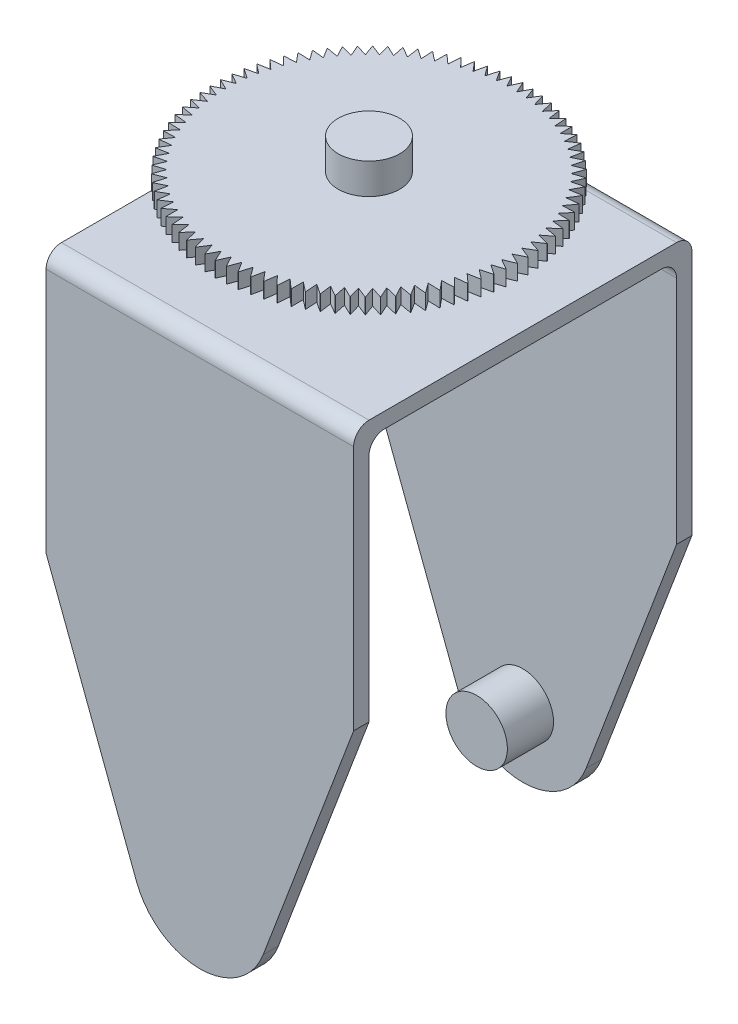
SolidWorks part; units mm, degrees
material "AISI 1035 Steel (SS)"
ref_plane "Front Plane" through (0, 0, 0) normal (0, 0, 1) x (1, 0, 0)
ref_plane "Top Plane" through (0, 0, 0) normal (0, 1, 0) x (1, 0, 0)
ref_plane "Right Plane" through (0, 0, 0) normal (1, 0, 0) x (0, 0, -1)
sketch "Sketch3" plane through (0, 0, 0) normal (0, 0, 1) x (1, 0, 0)
  line L0 (-50, 150) -> (50, 150)
  line L1 (50, 150) -> (50, 70)
  line L2 (50, 70) -> (20.5771, -7.7836)
  line L3 (-50, 150) -> (-50, 70)
  line L4 (-50, 70) -> (-20.5771, -7.7836)
  arc A0 (-20.5771, -7.7836) -> (20.5771, -7.7836) centre (0, 0) ccw
  point P7 (0, 150)
  dimension "D1" = 150
  dimension "D3" = 22
  dimension "D2" = 100
  dimension "D4" = 80
extrude "Boss-Extrude1" add sketch "Sketch3" along normal blind 5
sketch "Sketch4" plane through (0, 0, 5) normal (0, 0, 1) x (1, 0, 0)
  circle A0 centre (0, 0) radius 10
  dimension "D1" = 20
extrude "Boss-Extrude2" add sketch "Sketch4" along normal blind 15
sketch "Sketch5" plane through (0, 0, 0) normal (0, 0, -1) x (-1, 0, 0)
  line L0 (50, 150) -> (50, 70) construction
  line L1 (-50, 150) -> (50, 150)
  line L2 (-50, 150) -> (-50, 155)
  line L3 (-50, 155) -> (50, 155)
  line L4 (50, 150) -> (50, 155)
  dimension "D1" = 5
extrude "Boss-Extrude3" add sketch "Sketch5" against normal blind 55
mirror "Mirror1" about plane through (0, 0, 55) normal (0, 0, 1) of bodies 103
fillet "Fillet1" radius 5 4 edges at (0, 150, 105) (0, 150, 5) (0, 155, 110) (0, 155, 0)
sketch "Sketch6" plane through (0, 155, 0) normal (0, 1, 0) x (1, 0, 0)
  line L0 (50, -5) -> (-50, -5) construction
  line L1 (-50, -105) -> (-50, -5) construction
  circle A0 centre (0, -55) radius 12.5
  point P5 (0, -5)
  point P9 (-50, -55)
  dimension "D1" = 25
extrude "Boss-Extrude4" add sketch "Sketch6" along normal blind 5
sketch "Sketch7" plane through (0, 160, 0) normal (0, 1, 0) x (1, 0, 0)
  circle A0 centre (0, -55) radius 10
  circle A1 centre (0, -55) radius 12.5 construction
  dimension "D1" = 20
extrude "Boss-Extrude5" add sketch "Sketch7" along normal blind 5
sketch "Sketch8" plane through (0, 165, 0) normal (0, 1, 0) x (1, 0, 0)
  circle A0 centre (0, -55) radius 12.5 construction
  circle A1 centre (0, -55) radius 12.5
extrude "Boss-Extrude6" add sketch "Sketch8" along normal blind 5
sketch "Sketch9" plane through (0, 170, 0) normal (0, 1, 0) x (1, 0, 0)
  line L0 (0, -5) -> (1.5929, -8.5336)
  line L1 (1.5929, -8.5336) -> (3.4241, -5.1174)
  line L2 (4.8304, -8.7579) -> (6.8954, -5.4777)
  line L3 (3.4878, -5.1218) -> (4.8304, -8.7579)
  line L4 (8.0443, -9.2075) -> (10.3331, -6.0794)
  line L5 (6.9587, -5.4866) -> (8.0443, -9.2075)
  line L6 (11.219, -9.8802) -> (13.7204, -6.9193)
  line L7 (10.3956, -6.0926) -> (11.219, -9.8802)
  line L8 (14.3391, -10.7727) -> (17.0409, -7.9936)
  line L9 (13.7819, -6.9369) -> (14.3391, -10.7727)
  line L10 (17.3893, -11.8807) -> (20.2784, -9.2968)
  line L11 (17.101, -8.0154) -> (17.3893, -11.8807)
  line L12 (20.3548, -13.1987) -> (23.4171, -10.8227)
  line L13 (20.3368, -9.3227) -> (20.3548, -13.1987)
  line L14 (23.2211, -14.7204) -> (26.4417, -12.5638)
  line L15 (23.4736, -10.8526) -> (23.2211, -14.7204)
  line L16 (25.9743, -16.4384) -> (29.3375, -14.5116)
  line L17 (26.496, -12.5976) -> (25.9743, -16.4384)
  line L18 (28.601, -18.3442) -> (32.0904, -16.6567)
  line L19 (29.3893, -14.5492) -> (28.601, -18.3442)
  line L20 (31.0883, -20.4286) -> (34.6869, -18.9886)
  line L21 (32.1394, -16.6978) -> (31.0883, -20.4286)
  line L22 (33.4241, -22.6814) -> (37.1145, -21.496)
  line L23 (34.7329, -19.033) -> (33.4241, -22.6814)
  line L24 (35.5971, -25.0917) -> (39.3612, -24.1666)
  line L25 (37.1572, -21.5435) -> (35.5971, -25.0917)
  line L26 (37.5967, -27.6477) -> (41.4161, -26.9874)
  line L27 (39.4005, -24.2169) -> (37.5967, -27.6477)
  line L28 (39.4131, -30.3369) -> (43.2693, -29.9447)
  line L29 (41.4519, -27.0404) -> (39.4131, -30.3369)
  line L30 (41.0375, -33.1463) -> (44.9117, -33.024)
  line L31 (43.3013, -30) -> (41.0375, -33.1463)
  line L32 (42.462, -36.0622) -> (46.3352, -36.2104)
  line L33 (44.9397, -33.0814) -> (42.462, -36.0622)
  line L34 (43.6796, -39.0703) -> (47.533, -39.4884)
  line L35 (46.3592, -36.2697) -> (43.6796, -39.0703)
  line L36 (44.6844, -42.156) -> (48.4993, -42.8419)
  line L37 (47.5528, -39.5492) -> (44.6844, -42.156)
  line L38 (45.4715, -45.3044) -> (49.2293, -46.2547)
  line L39 (48.5148, -42.9039) -> (45.4715, -45.3044)
  line L40 (46.0371, -48.4999) -> (49.7194, -49.71)
  line L41 (49.2404, -46.3176) -> (46.0371, -48.4999)
  line L42 (46.3784, -51.7271) -> (49.9673, -53.1912)
  line L43 (49.7261, -49.7736) -> (46.3784, -51.7271)
  line L44 (46.4937, -54.9703) -> (49.9717, -56.6811)
  line L45 (49.9695, -53.255) -> (46.4937, -54.9703)
  line L46 (46.3825, -58.2136) -> (49.7327, -60.1629)
  line L47 (49.9695, -56.745) -> (46.3825, -58.2136)
  line L48 (46.0454, -61.4412) -> (49.2514, -63.6195)
  line L49 (49.7261, -60.2264) -> (46.0454, -61.4412)
  line L50 (45.4839, -64.6375) -> (48.5302, -67.0341)
  line L51 (49.2404, -63.6824) -> (45.4839, -64.6375)
  line L52 (44.7008, -67.7868) -> (47.5725, -70.3901)
  line L53 (48.5148, -67.0961) -> (44.7008, -67.7868)
  line L54 (43.6999, -70.8739) -> (46.3831, -73.6711)
  line L55 (47.5528, -70.4508) -> (43.6999, -70.8739)
  line L56 (42.4862, -73.8835) -> (44.9677, -76.8611)
  line L57 (46.3592, -73.7303) -> (42.4862, -73.8835)
  line L58 (41.0654, -76.8012) -> (43.3332, -79.9446)
  line L59 (44.9397, -76.9186) -> (41.0654, -76.8012)
  line L60 (39.4446, -79.6127) -> (41.4876, -82.9066)
  line L61 (43.3013, -80) -> (39.4446, -79.6127)
  line L62 (37.6317, -82.3043) -> (39.4398, -85.7327)
  line L63 (41.4519, -82.9596) -> (37.6317, -82.3043)
  line L64 (35.6353, -84.8628) -> (37.2, -88.409)
  line L65 (39.4005, -85.7831) -> (35.6353, -84.8628)
  line L66 (33.4654, -87.2759) -> (34.7789, -90.9226)
  line L67 (37.1572, -88.4565) -> (33.4654, -87.2759)
  line L68 (31.1324, -89.5317) -> (32.1883, -93.2611)
  line L69 (34.7329, -90.967) -> (31.1324, -89.5317)
  line L70 (28.6478, -91.6192) -> (29.4409, -95.4133)
  line L71 (32.1394, -93.3022) -> (28.6478, -91.6192)
  line L72 (26.0236, -93.5284) -> (26.5501, -97.3685)
  line L73 (29.3893, -95.4508) -> (26.0236, -93.5284)
  line L74 (23.2726, -95.2499) -> (23.53, -99.1173)
  line L75 (26.496, -97.4024) -> (23.2726, -95.2499)
  line L76 (20.4082, -96.7752) -> (20.3952, -100.6512)
  line L77 (23.4736, -99.1474) -> (20.4082, -96.7752)
  line L78 (17.4444, -98.0971) -> (17.161, -101.9627)
  line L79 (20.3368, -100.6773) -> (17.4444, -98.0971)
  line L80 (14.3956, -99.209) -> (13.8433, -103.0454)
  line L81 (17.101, -101.9846) -> (14.3956, -99.209)
  line L82 (11.2767, -100.1054) -> (10.4581, -103.8941)
  line L83 (13.7819, -103.0631) -> (11.2767, -100.1054)
  line L84 (8.1028, -100.7822) -> (7.0219, -104.5045)
  line L85 (10.3956, -103.9074) -> (8.1028, -100.7822)
  line L86 (4.8895, -101.2359) -> (3.5516, -104.8737)
  line L87 (6.9587, -104.5134) -> (4.8895, -101.2359)
  line L88 (1.6523, -101.4643) -> (0.0639, -105)
  line L89 (3.4878, -104.8782) -> (1.6523, -101.4643)
  line L90 (-1.5929, -101.4664) -> (-3.4241, -104.8826)
  line L91 (0, -105) -> (-1.5929, -101.4664)
  line L92 (-4.8304, -101.2421) -> (-6.8954, -104.5223)
  line L93 (-3.4878, -104.8782) -> (-4.8304, -101.2421)
  line L94 (-8.0443, -100.7925) -> (-10.3331, -103.9206)
  line L95 (-6.9587, -104.5134) -> (-8.0443, -100.7925)
  line L96 (-11.219, -100.1198) -> (-13.7204, -103.0807)
  line L97 (-10.3956, -103.9074) -> (-11.219, -100.1198)
  line L98 (-14.3391, -99.2273) -> (-17.0409, -102.0064)
  line L99 (-13.7819, -103.0631) -> (-14.3391, -99.2273)
  line L100 (-17.3893, -98.1193) -> (-20.2784, -100.7032)
  line L101 (-17.101, -101.9846) -> (-17.3893, -98.1193)
  line L102 (-20.3548, -96.8013) -> (-23.4171, -99.1773)
  line L103 (-20.3368, -100.6773) -> (-20.3548, -96.8013)
  line L104 (-23.2211, -95.2796) -> (-26.4417, -97.4362)
  line L105 (-23.4736, -99.1474) -> (-23.2211, -95.2796)
  line L106 (-25.9743, -93.5616) -> (-29.3375, -95.4884)
  line L107 (-26.496, -97.4024) -> (-25.9743, -93.5616)
  line L108 (-28.601, -91.6558) -> (-32.0904, -93.3433)
  line L109 (-29.3893, -95.4508) -> (-28.601, -91.6558)
  line L110 (-31.0883, -89.5714) -> (-34.6869, -91.0114)
  line L111 (-32.1394, -93.3022) -> (-31.0883, -89.5714)
  line L112 (-33.4241, -87.3186) -> (-37.1145, -88.504)
  line L113 (-34.7329, -90.967) -> (-33.4241, -87.3186)
  line L114 (-35.5971, -84.9083) -> (-39.3612, -85.8334)
  line L115 (-37.1572, -88.4565) -> (-35.5971, -84.9083)
  line L116 (-37.5967, -82.3523) -> (-41.4161, -83.0126)
  line L117 (-39.4005, -85.7831) -> (-37.5967, -82.3523)
  line L118 (-39.4131, -79.6631) -> (-43.2693, -80.0553)
  line L119 (-41.4519, -82.9596) -> (-39.4131, -79.6631)
  line L120 (-41.0375, -76.8537) -> (-44.9117, -76.976)
  line L121 (-43.3013, -80) -> (-41.0375, -76.8537)
  line L122 (-42.462, -73.9378) -> (-46.3352, -73.7896)
  line L123 (-44.9397, -76.9186) -> (-42.462, -73.9378)
  line L124 (-43.6796, -70.9297) -> (-47.533, -70.5116)
  line L125 (-46.3592, -73.7303) -> (-43.6796, -70.9297)
  line L126 (-44.6844, -67.844) -> (-48.4993, -67.1581)
  line L127 (-47.5528, -70.4508) -> (-44.6844, -67.844)
  line L128 (-45.4715, -64.6956) -> (-49.2293, -63.7453)
  line L129 (-48.5148, -67.0961) -> (-45.4715, -64.6956)
  line L130 (-46.0371, -61.5001) -> (-49.7194, -60.29)
  line L131 (-49.2404, -63.6824) -> (-46.0371, -61.5001)
  line L132 (-46.3784, -58.2729) -> (-49.9673, -56.8088)
  line L133 (-49.7261, -60.2264) -> (-46.3784, -58.2729)
  line L134 (-46.4937, -55.0297) -> (-49.9717, -53.3189)
  line L135 (-49.9695, -56.745) -> (-46.4937, -55.0297)
  line L136 (-46.3825, -51.7864) -> (-49.7327, -49.8371)
  line L137 (-49.9695, -53.255) -> (-46.3825, -51.7864)
  line L138 (-46.0454, -48.5588) -> (-49.2514, -46.3805)
  line L139 (-49.7261, -49.7736) -> (-46.0454, -48.5588)
  line L140 (-45.4839, -45.3625) -> (-48.5302, -42.9659)
  line L141 (-49.2404, -46.3176) -> (-45.4839, -45.3625)
  line L142 (-44.7008, -42.2132) -> (-47.5725, -39.6099)
  line L143 (-48.5148, -42.9039) -> (-44.7008, -42.2132)
  line L144 (-43.6999, -39.1261) -> (-46.3831, -36.3289)
  line L145 (-47.5528, -39.5492) -> (-43.6999, -39.1261)
  line L146 (-42.4862, -36.1165) -> (-44.9677, -33.1389)
  line L147 (-46.3592, -36.2697) -> (-42.4862, -36.1165)
  line L148 (-41.0654, -33.1988) -> (-43.3332, -30.0554)
  line L149 (-44.9397, -33.0814) -> (-41.0654, -33.1988)
  line L150 (-39.4446, -30.3873) -> (-41.4876, -27.0934)
  line L151 (-43.3013, -30) -> (-39.4446, -30.3873)
  line L152 (-37.6317, -27.6957) -> (-39.4398, -24.2673)
  line L153 (-41.4519, -27.0404) -> (-37.6317, -27.6957)
  line L154 (-35.6353, -25.1372) -> (-37.2, -21.591)
  line L155 (-39.4005, -24.2169) -> (-35.6353, -25.1372)
  line L156 (-33.4654, -22.7241) -> (-34.7789, -19.0774)
  line L157 (-37.1572, -21.5435) -> (-33.4654, -22.7241)
  line L158 (-31.1324, -20.4683) -> (-32.1883, -16.7389)
  line L159 (-34.7329, -19.033) -> (-31.1324, -20.4683)
  line L160 (-28.6478, -18.3808) -> (-29.4409, -14.5867)
  line L161 (-32.1394, -16.6978) -> (-28.6478, -18.3808)
  line L162 (-26.0236, -16.4716) -> (-26.5501, -12.6315)
  line L163 (-29.3893, -14.5492) -> (-26.0236, -16.4716)
  line L164 (-23.2726, -14.7501) -> (-23.53, -10.8827)
  line L165 (-26.496, -12.5976) -> (-23.2726, -14.7501)
  line L166 (-20.4082, -13.2248) -> (-20.3952, -9.3488)
  line L167 (-23.4736, -10.8526) -> (-20.4082, -13.2248)
  line L168 (-17.4444, -11.9029) -> (-17.161, -8.0373)
  line L169 (-20.3368, -9.3227) -> (-17.4444, -11.9029)
  line L170 (-14.3956, -10.791) -> (-13.8433, -6.9546)
  line L171 (-17.101, -8.0154) -> (-14.3956, -10.791)
  line L172 (-11.2767, -9.8946) -> (-10.4581, -6.1059)
  line L173 (-13.7819, -6.9369) -> (-11.2767, -9.8946)
  line L174 (-8.1028, -9.2178) -> (-7.0219, -5.4955)
  line L175 (-10.3956, -6.0926) -> (-8.1028, -9.2178)
  line L176 (-4.8895, -8.7641) -> (-3.5516, -5.1263)
  line L177 (-6.9587, -5.4866) -> (-4.8895, -8.7641)
  line L178 (-1.6523, -8.5357) -> (-0.0639, -5)
  line L179 (-3.4878, -5.1218) -> (-1.6523, -8.5357)
  circle A0 centre (0, -55) radius 50
  point P276 (0, -55)
  circle M3 centre (0, -55) radius 12.5
  dimension "D1" = 100
  dimension "D2" = 90
  dimension "D3" = 3.876
extrude "Boss-Extrude7" add sketch "Sketch9" along normal blind 5 contours L91 A0 L88 L89 L86 L87 L84 L85 L82 L83 L80 L81 L78 L79 L76 L77 L74 L75 L72 L73 L70 L71 L68 L69 L66 L67 L64 L65 L62 L63 L60 L61 L58 L59 L56 | M3 region at (-0.4924, 170, 7.3478) region at (0, 170, 55)
sketch "Sketch10" plane through (0, 175, 0) normal (0, 1, 0) x (1, 0, 0)
  circle A0 centre (0, -55) radius 10
  circle A1 centre (0, -55) radius 10 construction
  point P2 (0, 0)
  dimension "D1" = 20
extrude "Boss-Extrude8" add sketch "Sketch10" along normal blind 10
